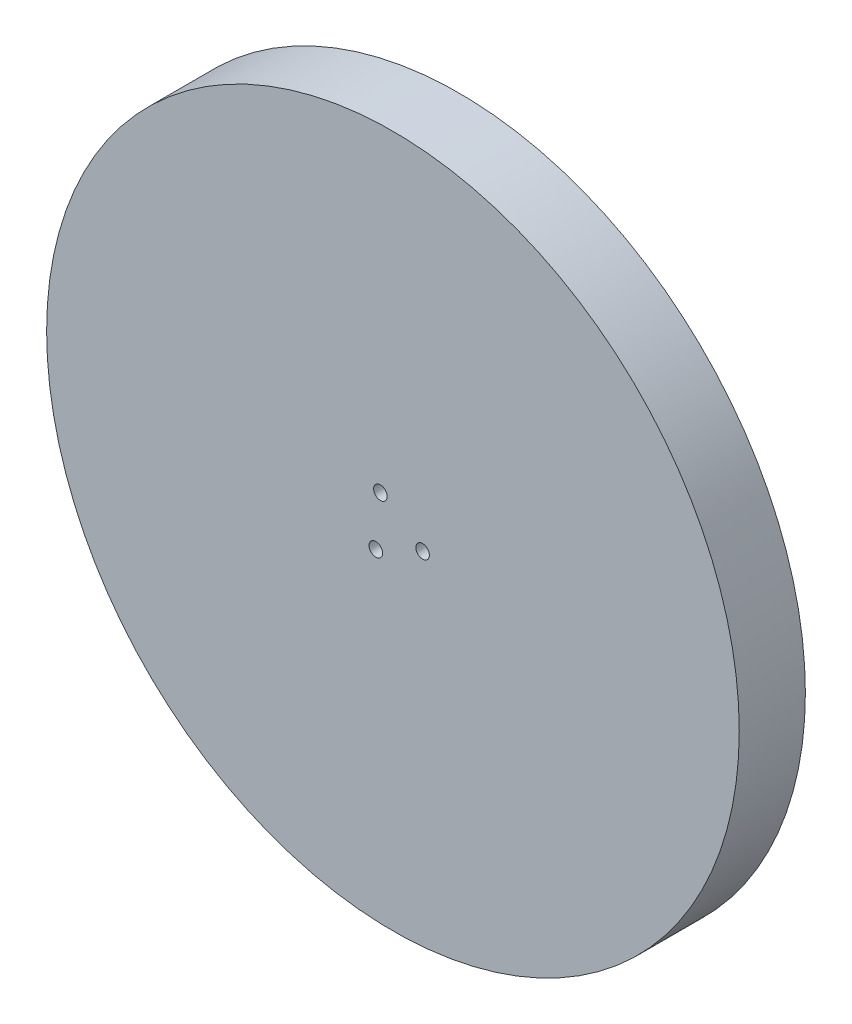
SolidWorks part; units mm, degrees
ref_plane "Front Plane" through (0, 0, 0) normal (0, 0, 1) x (1, 0, 0)
ref_plane "Top Plane" through (0, 0, 0) normal (0, 1, 0) x (1, 0, 0)
ref_plane "Right Plane" through (0, 0, 0) normal (1, 0, 0) x (0, 0, -1)
sketch "Sketch1" plane through (0, 0, 0) normal (0, 0, 1) x (1, 0, 0)
  circle A0 centre (0, 0) radius 52.3715
extrude "Boss-Extrude1" add sketch "Sketch1" along normal blind 10
hole_wizard "Ø2.05 (2.05) Diameter Hole1" positions "Sketch3" profile "Sketch4" hole size "Ø2.05" standard "ISO" end condition through all
sketch "Sketch3" plane through (-27.9652, -165.9867, 75.1531) normal (0, 0, 1) x (1, 0, 0)
  circle A0 centre (27.9652, 165.9867) radius 4.5
  point P0 (32.4472, 165.5842)
  point P2 (25.3756, 162.3065)
  point P4 (26.0728, 170.0695)
sketch "Sketch4" plane through (4.482, -0.4025, 75.1531) normal (1, 0, 0) x (0, -1, 0)
  line L0 (0, 0) -> (0, 75.1531)
  line L1 (0, 75.1531) -> (1.025, 75.1531)
  line L2 (1.025, 75.1531) -> (1.025, 0)
  line L3 (1.025, 0) -> (0, 0)
  line L4 (0, -6.35) -> (0, 107.95) construction
  dimension "Thru Hole Dia." = 2.05
  dimension "Thru Hole Depth" = 75.1531
